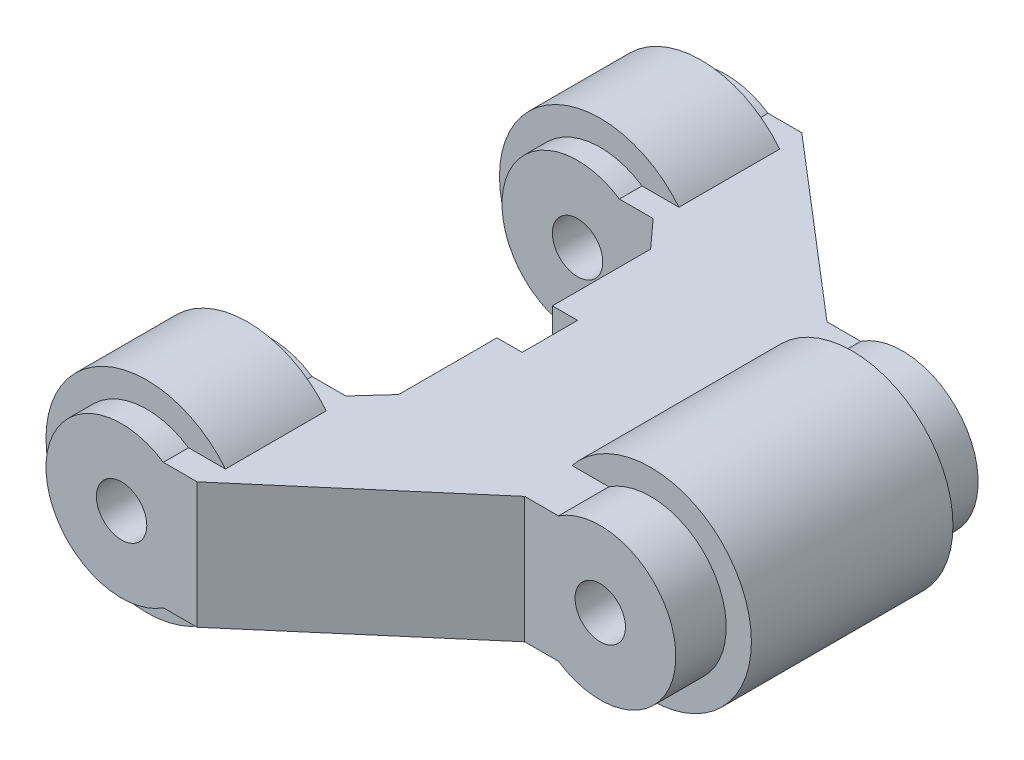
SolidWorks part; units mm, degrees
material "ABS"
ref_plane "Спереди" through (0, 0, 0) normal (0, 0, 1) x (1, 0, 0)
ref_plane "Сверху" through (0, 0, 0) normal (0, 1, 0) x (1, 0, 0)
ref_plane "Справа" through (0, 0, 0) normal (1, 0, 0) x (0, 0, -1)
sketch "Эскиз1" plane through (0, 0, 0) normal (0, 0, 1) x (1, 0, 0)
  line L0 (0, 6.8428) -> (0, -6.3335) construction
  line L3 (-18.7141, 0) -> (20.1145, 0) construction
  circle A0 centre (-6.5, 0) radius 3
  circle A1 centre (6.5, 0) radius 3
  circle A3 centre (6.5, 0) radius 4
  circle A4 centre (-6.5, 0) radius 1
  circle A5 centre (6.5, 0) radius 1
  dimension "D1" = 6
  dimension "D2" = 8
  dimension "D5" = 2
  dimension "D4" = 13
extrude "Бобышка-Вытянуть1" add sketch "Эскиз1" along normal mid plane 12 contours A1 A5 region at (3.5849, 0, 0)
extrude "Бобышка-Вытянуть2" add sketch "Эскиз1<4>" along normal mid plane 8 contours A3 A1 region at (2.6131, 0, 0)
sketch "Эскиз1<4>" plane through (0, 0, 0) normal (0, 0, 1) x (1, 0, 0) same geometry as "Эскиз1"
extrude "Бобышка-Вытянуть3" add sketch "Эскиз1<5>" along normal mid plane 24 separate body contours A0 A4 region at (-9.4151, 0, 0)
sketch "Эскиз1<5>" plane through (0, 0, 0) normal (0, 0, 1) x (1, 0, 0) same geometry as "Эскиз1"
ref_plane "Плоскость1" through (0, 0, 9) normal (0, 0, 1) x (1, 0, 0)
sketch "Эскиз2" plane through (0, 0, 9) normal (0, 0, 1) x (1, 0, 0)
  circle A1 centre (-6.5, 0) radius 4
  circle A4 centre (-6.5, 0) radius 3 construction
  circle A5 centre (-6.5, 0) radius 3
  dimension "D1" = 8
extrude "Бобышка-Вытянуть4" add sketch "Эскиз2" along normal mid plane 4
mirror "Зеркальное отражение1" about plane through (0, 0, 0) normal (0, 0, 1) of "Бобышка-Вытянуть4"
sketch "Эскиз3" plane through (0, 0, 0) normal (0, 1, 0) x (1, 0, 0)
  line L0 (-13.7421, 0) -> (15.3447, 0) construction
  line L1 (-9.5, 7) -> (-9.5, -7) construction
  line L2 (-9.5, 6.1) -> (-3.5, 6.1)
  line L3 (-9.5, 6.1) -> (-9.5, -6.1)
  line L4 (-9.5, -6.1) -> (-3.5, -6.1)
  line L5 (-3.5, 6.1) -> (-3.5, -6.1)
  line L6 (-3.5, -7) -> (-3.5, 7) construction
  dimension "D1" = 12.2
extrude "Вырез-Вытянуть1" cut sketch "Эскиз3" against normal through all both and the other way through all
sketch "Эскиз4" plane through (0, 0, 0) normal (0, 1, 0) x (1, 0, 0)
  line L0 (9.5, 6) -> (3.5, 6) construction
  line L1 (9.5, 6) -> (3.5, 6)
  line L3 (5.5, 6) -> (5.5, -6) construction
  line L4 (-5.5, -12) -> (-5.5, -6.1) construction
  line L5 (-5.5, -12) -> (-5.5, -6.1)
  line L6 (-3.5, -12) -> (3.5, -6)
  line L7 (-18.3896, 0) -> (15.2245, 0) construction
  line L8 (-3.5, 12) -> (3.5, 6)
  line L10 (-5.5, -12) -> (-5.5, 12)
  line L11 (-3.5, 12) -> (-9.5, 12) construction
  line L13 (-5.5, 12) -> (-3.5, 12)
  line L14 (-5.5, -12) -> (-3.5, -12)
  line L24 (5.5, 6) -> (5.5, -6)
  line L25 (3.5, 6) -> (5.5, 6)
  line L26 (3.5, -6) -> (5.5, -6)
  line L27 (-9.5, -12) -> (-3.5, -12) construction
  line L30 (-3.5, 6.1) -> (-2.5, 5)
  line L31 (-2.5, 5) -> (-2.5, -5)
  line L33 (-2.5, -5) -> (-3.5, -6.1)
  line L34 (-3.5, -6.1) -> (-9.5, -6.1) construction
  line L35 (-3.5, -7) -> (-3.5, -6.1) construction
  line L36 (-3.5, -6.1) -> (-5.5, -6.1)
  line L37 (-3.5, 6.1) -> (-5.5, 6.1)
  line L38 (-9.5, -12) -> (-3.5, -12)
  line L39 (-6.5, 12) -> (-6.5, -12) construction
  dimension "D1" = 8
  dimension "D2" = 10
extrude "Бобышка-Вытянуть7" add sketch "Эскиз4" along normal mid plane 5 contours L31 L7 L24 L25 L8 L13 L10 L37 L30 region at (-0.0844, 0, 0)
sketch "Эскиз5" plane through (0, 0, 0) normal (0, 0, 1) x (1, 0, 0)
  line L0 (-2.5, -2.5) -> (-2.5, 2.5)
  line L1 (-3.5, -2.5) -> (3.5, -2.5) construction
  line L2 (-3.5, 2.5) -> (3.5, 2.5) construction
  line L3 (-2.5, 2.5) -> (-1.5, 2.5)
  line L4 (-1.5, 2.5) -> (-2.5, -2.5)
  line L5 (-2.5, 2.5) -> (-2.5, -2.5) construction
  line L6 (-2.5, 2.5) -> (-2.5, -2.5)
  dimension "D1" = 1
extrude "Вырез-Вытянуть2" cut sketch "Эскиз5" against normal mid plane 2.2 contours L4 L3 L0 region at (-2.1667, 0.8333, 0)
